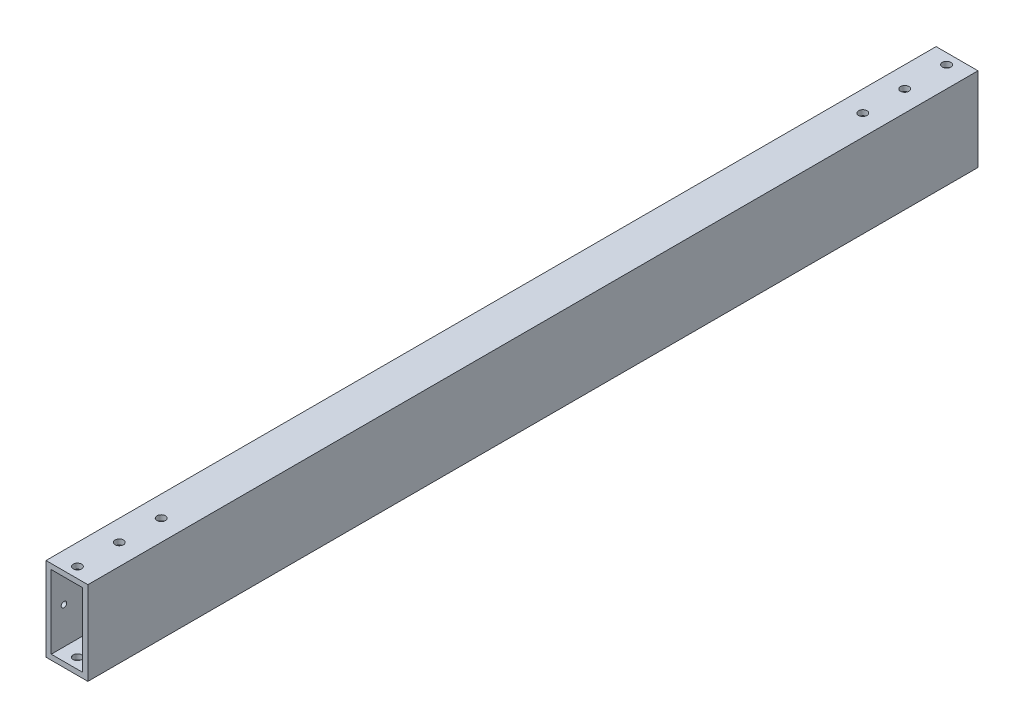
SolidWorks part; units mm, degrees
material "6061-T6 (SS)"
ref_plane "Front" through (0, 0, 0) normal (0, 0, 1) x (1, 0, 0)
ref_plane "Top" through (0, 0, 0) normal (0, 1, 0) x (1, 0, 0)
ref_plane "Right" through (0, 0, 0) normal (1, 0, 0) x (0, 0, -1)
sketch "Sketch1" plane through (0, 0, 0) normal (0, 0, 1) x (1, 0, 0)
  line L1 (-12.7, -25.4) -> (12.7, -25.4)
  line L2 (-12.7, -25.4) -> (-12.7, 25.4)
  line L3 (-12.7, 25.4) -> (12.7, 25.4)
  line L4 (12.7, -25.4) -> (12.7, 25.4)
  line L5 (-12.7, -25.4) -> (12.7, 25.4) construction
  line L6 (-12.7, 25.4) -> (12.7, -25.4) construction
  point P0 (0, 0)
  dimension "D1" = 25.4
  dimension "D2" = 50.8
extrude "Extrude-Thin1" add sketch "Sketch1" along normal blind 539.75 thin thin type one direction reverse wall 3.175
hole_wizard "#10 Clearance Hole1" positions "Sketch2" profile "Sketch3" hole size "#10" standard "ANSI Inch" end condition through all
sketch "Sketch2" plane through (0, 25.4, 0) normal (0, 1, 0) x (1, 0, 0)
  line L0 (-12.7, -539.75) -> (-12.7, 0) construction
  line L1 (12.7, -539.75) -> (-12.7, -539.75) construction
  point P0 (0, -533.4)
  point P2 (0, -508)
  point P4 (0, -482.6)
  point P6 (0, -6.35)
  point P8 (0, -31.75)
  point P10 (0, -57.15)
  dimension "D1" = 12.7
  dimension "D2" = 25.4
  dimension "D3" = 6.35
  dimension "D4" = 25.4
  dimension "D5" = 6.35
  dimension "D6" = 25.4
  dimension "D7" = 25.4
sketch "Sketch3" plane through (0, 25.4, 533.4) normal (1, 0, 0) x (0, 0, 1)
  line L0 (0, 0) -> (0, 50.8)
  line L1 (0, 50.8) -> (2.5527, 50.8)
  line L2 (2.5527, 50.8) -> (2.5527, 0)
  line L5 (2.5527, 0) -> (0, 0)
  line L11 (0, -6.35) -> (0, 107.95) construction
  dimension "Thru Hole Dia." = 5.1054
  dimension "Thru Hole Depth" = 50.8
sketch "Sketch6" plane through (-12.7, 0, 0) normal (-1, 0, 0) x (0, 0, 1)
  point P0 (172.05, 0)
  point P3 (112.05, 0)
  point P6 (52.05, 0)
  point P9 (232.05, 0)
  point P12 (292.05, 0)
  point P15 (352.05, 0)
  point P18 (412.05, 0)
  point P21 (472.05, 0)
  point P24 (532.05, 0)
hole_wizard "M4x0.7 Tapped Hole1" positions "Sketch6" profile "Sketch5" tap size "M4x0.7" standard "ANSI Metric" end condition up to next
cosmetic thread "Hole Thread1" parameters "D2"=4
cosmetic thread "Hole Thread2" parameters "D2"=4
cosmetic thread "Hole Thread3" parameters "D2"=4
cosmetic thread "Hole Thread4" parameters "D2"=4
cosmetic thread "Hole Thread5" parameters "D2"=4
cosmetic thread "Hole Thread6" parameters "D2"=4
cosmetic thread "Hole Thread7" parameters "D2"=4
cosmetic thread "Hole Thread8" parameters "D2"=4
cosmetic thread "Hole Thread9" parameters "D2"=4
sketch "Sketch5" plane through (-12.7, 0, 172.05) normal (0, 1, 0) x (0, 0, 1)
  line L0 (0, 0) -> (0, 3.175)
  line L1 (0, 3.175) -> (1.65, 3.175)
  line L2 (1.65, 3.175) -> (1.65, 0)
  line L5 (1.65, 0) -> (0, 0)
  line L11 (0, -6.35) -> (0, 107.95) construction
  dimension "Thru Tap Drill Dia." = 3.3
  dimension "Thru Tap Drill Depth" = 3.175
sketch "Sketch9" plane through (0, -25.4, 0) normal (0, -1, 0) x (-1, 0, 0)
  circle A1 centre (3.175, -298.958) radius 1.651 construction
  point P0 (3.175, -70.358)
  point P3 (-3.175, -95.758)
  point P6 (3.175, -127.508)
  point P9 (-3.175, -152.908)
  point P12 (3.175, -184.658)
  point P19 (3.175, -241.808)
  point P22 (-3.175, -267.208)
  point P25 (4.826, -298.958)
  point P29 (-3.175, -324.358)
  point P32 (3.175, -356.108)
  point P35 (-3.175, -381.508)
  point P38 (3.175, -413.258)
  point P41 (-3.175, -438.658)
  point P44 (3.175, -470.408)
  point P50 (-3.175, -210.058)
hole_wizard "1/8 (0.13) Diameter Hole1" positions "Sketch9" profile "Sketch8" hole size "1/8" standard "ANSI Inch" end condition up to next
sketch "Sketch8" plane through (-3.175, -25.4, 70.358) normal (1, 0, 0) x (0, 0, -1)
  line L0 (0, 0) -> (0, 3.175)
  line L1 (0, 3.175) -> (1.651, 3.175)
  line L2 (1.651, 3.175) -> (1.651, 0)
  line L5 (1.651, 0) -> (0, 0)
  line L11 (0, -6.35) -> (0, 107.95) construction
  dimension "Thru Hole Dia." = 3.302
  dimension "Thru Hole Depth" = 3.175
